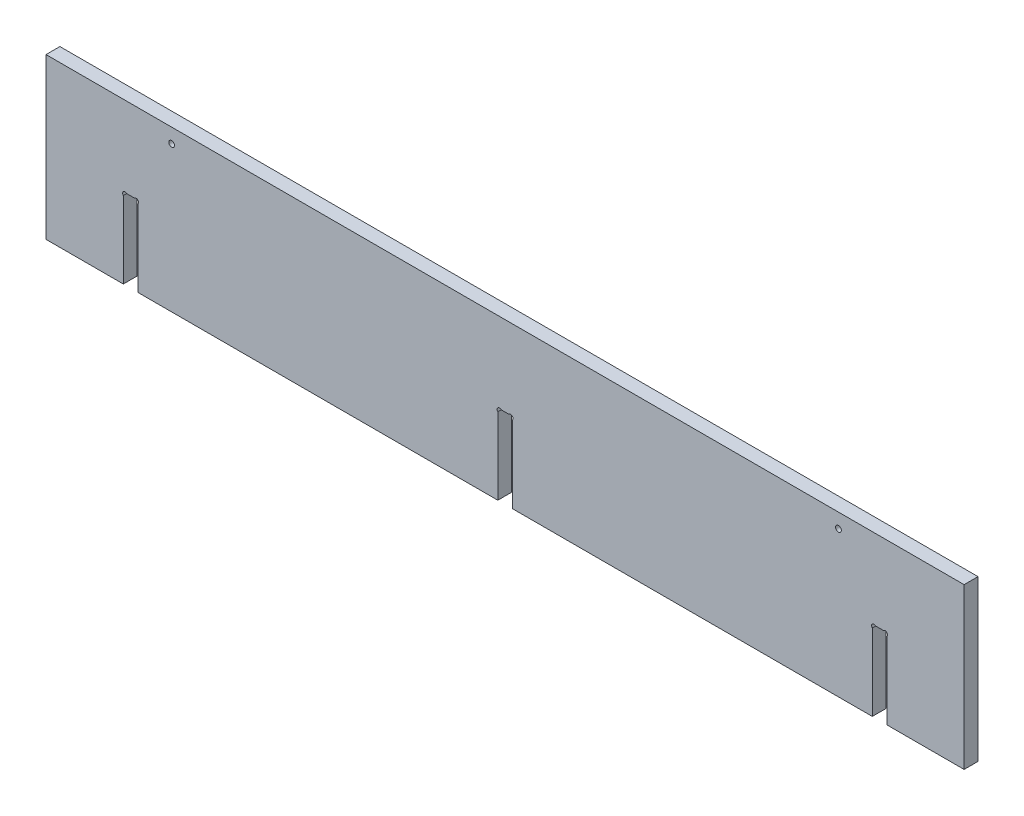
SolidWorks part; units mm, degrees
material "Pine"
ref_plane "Front Plane" through (0, 0, 0) normal (0, 0, 1) x (1, 0, 0)
ref_plane "Top Plane" through (0, 0, 0) normal (0, 1, 0) x (1, 0, 0)
ref_plane "Right Plane" through (0, 0, 0) normal (1, 0, 0) x (0, 0, -1)
sketch "Sketch1" plane through (0, 0, 0) normal (0, 0, 1) x (1, 0, 0)
  line L0 (206.0456, 84.1325) -> (206.0456, 117.4692) construction
  line L1 (-483.6817, 294.4762) -> (405.3183, 294.4762)
  line L3 (-459.0754, 84.1325) -> (13.9996, 84.1325)
  line L7 (-473.6353, 189.2885) -> (-463.5655, 189.2885)
  line L8 (-459.0754, 84.1325) -> (-459.0754, 184.7984)
  line L9 (626.7746, 294.4762) -> (23.5246, 294.4762) construction
  line L12 (520.6845, 189.2885) -> (510.6147, 189.2885)
  line L13 (506.1246, 84.1325) -> (506.1246, 184.7984)
  line L14 (-483.6817, 294.4762) -> (-579.7254, 294.4762)
  line L15 (-478.1254, 184.7984) -> (-478.1254, 84.1325)
  line L16 (-478.1254, 84.1325) -> (-579.7254, 84.1325)
  line L17 (-579.7254, 294.4762) -> (-579.7254, 84.1325)
  line L18 (405.3183, 294.4762) -> (626.7746, 294.4762)
  line L19 (525.1746, 184.7984) -> (525.1746, 84.1325)
  line L20 (525.1746, 84.1325) -> (626.7746, 84.1325)
  line L21 (626.7746, 294.4762) -> (626.7746, 84.1325)
  line L22 (23.5246, 294.4762) -> (23.5246, 189.2885) construction
  line L23 (23.5246, 189.2885) -> (28.5595, 189.2885) construction
  line L24 (33.0496, 84.1325) -> (506.1246, 84.1325)
  line L25 (28.5595, 189.2885) -> (18.4897, 189.2885)
  line L26 (33.0496, 184.7984) -> (33.0496, 84.1325)
  line L28 (13.9996, 184.7984) -> (13.9996, 84.1325)
  arc A2 (33.0496, 184.7984) -> (28.5595, 189.2885) centre (30.8045, 187.0434) ccw
  arc A3 (18.4897, 189.2885) -> (13.9996, 184.7984) centre (16.2447, 187.0434) ccw
  arc A4 (-459.0754, 184.7984) -> (-463.5655, 189.2885) centre (-461.3205, 187.0434) ccw
  arc A5 (-473.6353, 189.2885) -> (-478.1254, 184.7984) centre (-475.8803, 187.0434) ccw
  arc A6 (525.1746, 184.7984) -> (520.6845, 189.2885) centre (522.9295, 187.0434) ccw
  arc A8 (510.6147, 189.2885) -> (506.1246, 184.7984) centre (508.3697, 187.0434) ccw
  dimension "D1" = 965.2
  dimension "D2" = 210.3438
  dimension "D3" = 105.156
  dimension "D5" = 105.156
  dimension "D6" = 105.156
  dimension "D7" = 101.6
  dimension "D8" = 101.6
  dimension "D9" = 210.3438
  dimension "D10" = 210.3438
  dimension "D11" = 1206.5
  dimension "D12" = 603.25
extrude "Boss-Extrude1" add sketch "Sketch1" along normal blind 18.2562
hole_wizard "19/64 (0.29688) Diameter Hole1" positions "Sketch2" profile "Sketch3" hole size "19/64" standard "ANSI Inch" end condition through all
sketch "Sketch2" plane through (0, 0, 0) normal (0, 0, -1) x (-1, 0, 0)
  line L0 (-626.7746, 294.4762) -> (579.7254, 294.4762) construction
  line L1 (-506.1246, 84.1325) -> (-506.1246, 184.7984) construction
  line L2 (459.0754, 184.7984) -> (459.0754, 84.1325) construction
  point P0 (-461.6746, 275.4262)
  point P2 (414.6254, 275.4262)
  dimension "D1" = 19.05
  dimension "D2" = 44.45
  dimension "D3" = 19.05
  dimension "D4" = 44.45
sketch "Sketch3" plane through (461.6746, 275.4262, 0) normal (1, 0, 0) x (0, 1, 0)
  line L0 (0, 0) -> (0, 18.2562)
  line L1 (0, 18.2562) -> (3.7704, 18.2562)
  line L2 (3.7704, 18.2562) -> (3.7704, 0)
  line L5 (3.7704, 0) -> (0, 0)
  line L11 (0, -6.35) -> (0, 107.95) construction
  dimension "Thru Hole Dia." = 7.5408
  dimension "Thru Hole Depth" = 18.2562
